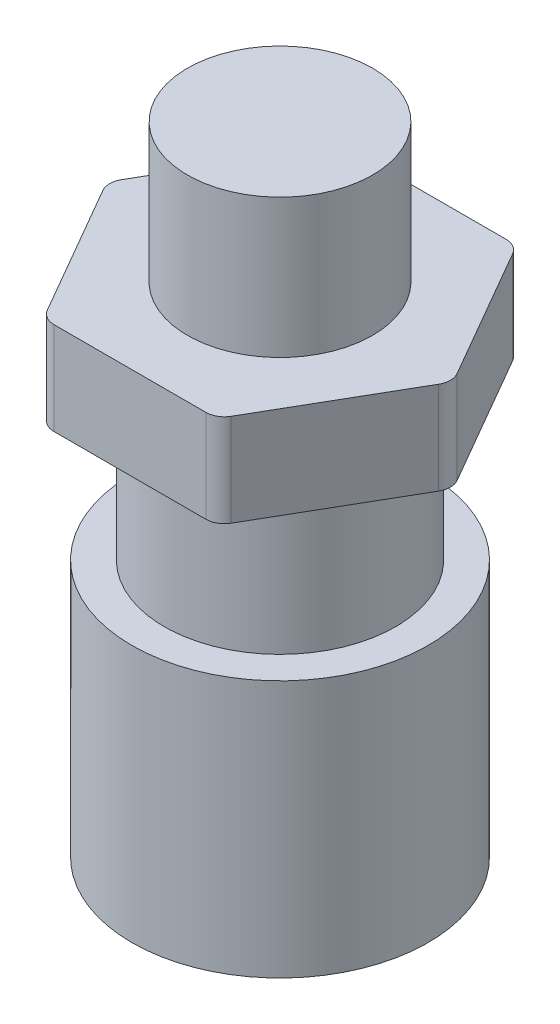
SolidWorks part; units mm, degrees
ref_plane "Front Plane" through (0, 0, 0) normal (0, 0, 1) x (1, 0, 0)
ref_plane "Top Plane" through (0, 0, 0) normal (0, 1, 0) x (1, 0, 0)
ref_plane "Right Plane" through (0, 0, 0) normal (1, 0, 0) x (0, 0, -1)
sketch "Sketch1" plane through (0, 0, 0) normal (0, 1, 0) x (1, 0, 0)
  line L0 (-20.574, 0) -> (20.574, 0) construction
  line L1 (-10.287, 17.8176) -> (10.287, -17.8176) construction
  line L2 (10.287, 17.8176) -> (-10.287, -17.8176) construction
  line L3 (20.574, 0) -> (-20.574, 0) construction
  line L4 (10.287, -17.8176) -> (-10.287, 17.8176) construction
  line L5 (-10.287, -17.8176) -> (10.287, 17.8176) construction
  line L6 (-11.8784, 20.574) -> (11.8784, 20.574)
  line L7 (11.8784, 20.574) -> (23.7568, 0)
  line L8 (23.7568, 0) -> (11.8784, -20.574)
  line L9 (11.8784, -20.574) -> (-11.8784, -20.574)
  line L10 (-11.8784, -20.574) -> (-23.7568, 0)
  line L11 (-23.7568, 0) -> (-11.8784, 20.574)
  circle A0 centre (0, 0) radius 20.574 construction
  point P17 (0, 0)
  dimension "D1" = 41.148
  dimension "D2" = 6
extrude "Boss-Extrude1" add sketch "Sketch1" along normal blind 12.7
fillet "Fillet1" radius 2.54 6 edges at (-11.8784, 6.35, 20.574) (-23.7568, 6.35, 0) (-11.8784, 6.35, -20.574) (11.8784, 6.35, -20.574) (11.8784, 6.35, 20.574) (23.7568, 6.35, 0)
sketch "Sketch2" plane through (0, 0, 0) normal (0, -1, 0) x (1, 0, 0)
  circle A0 centre (0, 0) radius 20.32
  dimension "D1" = 40.64
extrude "Boss-Extrude4" add sketch "Sketch2" along normal blind 55.626
sketch "Sketch4" plane through (0, 0, 0) normal (0, -1, 0) x (1, 0, 0)
  line L6 (10.4119, 20.574) -> (-10.4119, 20.574)
  line L7 (-12.6116, 19.304) -> (-23.0236, 1.27)
  line L8 (-23.0236, -1.27) -> (-12.6116, -19.304)
  line L9 (-10.4119, -20.574) -> (10.4119, -20.574)
  line L10 (12.6116, -19.304) -> (23.0236, -1.27)
  line L11 (23.0236, 1.27) -> (12.6116, 19.304)
  line L12 (10.4119, 20.574) -> (-10.4119, 20.574)
  line L13 (-12.6116, 19.304) -> (-23.0236, 1.27)
  line L14 (-23.0236, -1.27) -> (-12.6116, -19.304)
  line L15 (-10.4119, -20.574) -> (10.4119, -20.574)
  line L16 (12.6116, -19.304) -> (23.0236, -1.27)
  line L17 (23.0236, 1.27) -> (12.6116, 19.304)
  circle A0 centre (0, 0) radius 20.32 construction
  circle A1 centre (0, 0) radius 20.32
  circle A2 centre (0, 0) radius 15.875
  arc A6 (-10.4119, 20.574) -> (-12.6116, 19.304) centre (-10.4119, 18.034) ccw
  arc A7 (-23.0236, 1.27) -> (-23.0236, -1.27) centre (-20.8239, 0) ccw
  arc A8 (-12.6116, -19.304) -> (-10.4119, -20.574) centre (-10.4119, -18.034) ccw
  arc A9 (10.4119, -20.574) -> (12.6116, -19.304) centre (10.4119, -18.034) ccw
  arc A10 (23.0236, -1.27) -> (23.0236, 1.27) centre (20.8239, 0) ccw
  arc A11 (12.6116, 19.304) -> (10.4119, 20.574) centre (10.4119, 18.034) ccw
  arc A12 (-10.4119, 20.574) -> (-12.6116, 19.304) centre (-10.4119, 18.034) ccw
  arc A13 (-23.0236, 1.27) -> (-23.0236, -1.27) centre (-20.8239, 0) ccw
  arc A14 (-12.6116, -19.304) -> (-10.4119, -20.574) centre (-10.4119, -18.034) ccw
  arc A15 (10.4119, -20.574) -> (12.6116, -19.304) centre (10.4119, -18.034) ccw
  arc A16 (23.0236, -1.27) -> (23.0236, 1.27) centre (20.8239, 0) ccw
  arc A17 (12.6116, 19.304) -> (10.4119, 20.574) centre (10.4119, 18.034) ccw
  circle M13 centre (0, 0) radius 20.32
  dimension "D2" = 31.75
  dimension "D1" = 0
extrude "Cut-Extrude1" cut sketch "Sketch4" along normal blind 20.32 contours A2 M13 region at (-19.7453, 0, 0)
sketch "Sketch5" plane through (0, 12.7, 0) normal (0, 1, 0) x (1, 0, 0)
  circle A0 centre (0, 0) radius 12.7
  dimension "D1" = 25.4
extrude "Boss-Extrude5" add sketch "Sketch5" along normal blind 19.05
